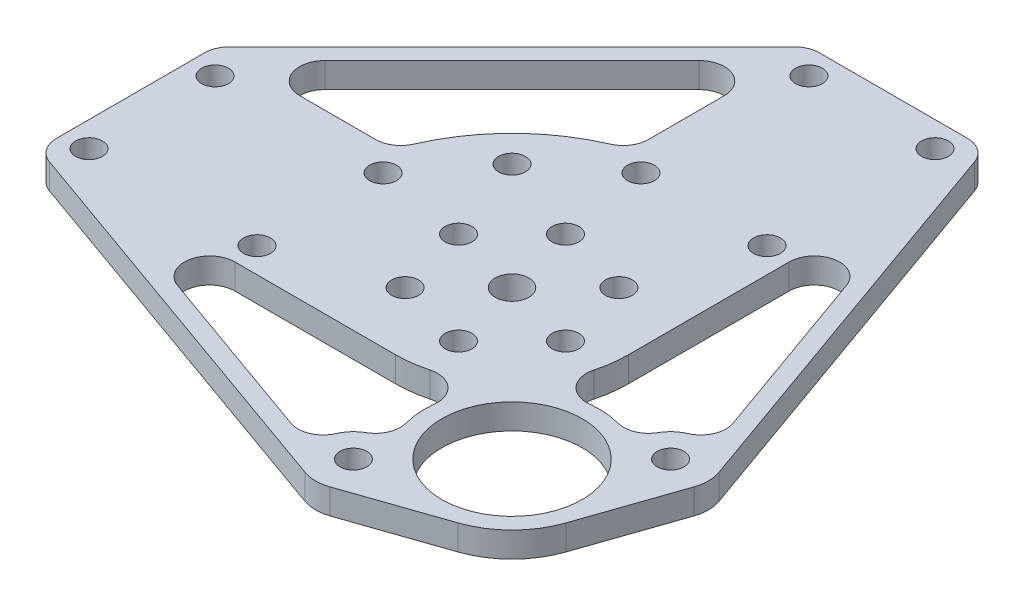
SolidWorks part; units mm, degrees
material "6061-T6 (SS)"
ref_plane "Front Plane" through (0, 0, 0) normal (0, 0, 1) x (1, 0, 0)
ref_plane "Top Plane" through (0, 0, 0) normal (0, 1, 0) x (1, 0, 0)
ref_plane "Right Plane" through (0, 0, 0) normal (1, 0, 0) x (0, 0, -1)
sketch "Sketch1" plane through (0, 0, 0) normal (0, 1, 0) x (1, 0, 0)
  line L0 (-14.5, -32) -> (14.5, -32) construction
  line L1 (10.85, 19.5) -> (-4.15, 19.5)
  line L2 (10.85, 19.5) -> (10.85, 39.5)
  line L3 (10.85, 39.5) -> (-4.15, 39.5)
  line L4 (-4.15, 19.5) -> (-4.15, 39.5)
  line L5 (10.85, 19.5) -> (-4.15, 39.5) construction
  line L6 (10.85, 39.5) -> (-4.15, 19.5) construction
  line L7 (-19.5, -10.85) -> (-39.5, -10.85)
  line L8 (-19.5, -10.85) -> (-19.5, 4.15)
  line L9 (-19.5, 4.15) -> (-39.5, 4.15)
  line L10 (-39.5, -10.85) -> (-39.5, 4.15)
  line L11 (-19.5, -10.85) -> (-39.5, 4.15) construction
  line L12 (-19.5, 4.15) -> (-39.5, -10.85) construction
  line L13 (20.7, 16) -> (-14, 16)
  line L14 (20.7, 16) -> (20.7, 43)
  line L15 (20.7, 43) -> (-14, 43)
  line L16 (-14, 16) -> (-14, 43)
  line L17 (20.7, 16) -> (-14, 43) construction
  line L18 (20.7, 43) -> (-14, 16) construction
  line L19 (-16, -20.7) -> (-43, -20.7)
  line L20 (-16, -20.7) -> (-16, 14)
  line L21 (-16, 14) -> (-43, 14)
  line L22 (-43, -20.7) -> (-43, 14)
  line L23 (-16, -20.7) -> (-43, 14) construction
  line L24 (-16, 14) -> (-43, -20.7) construction
  line L25 (10, -37) -> (-10, -37)
  line L26 (10, -37) -> (10, -27)
  line L27 (10, -27) -> (-10, -27)
  line L28 (-10, -37) -> (-10, -27)
  line L29 (10, -37) -> (-10, -27) construction
  line L30 (10, -27) -> (-10, -37) construction
  line L31 (37, -10) -> (27, -10)
  line L32 (37, -10) -> (37, 10)
  line L33 (37, 10) -> (27, 10)
  line L34 (27, -10) -> (27, 10)
  line L35 (37, -10) -> (27, 10) construction
  line L36 (37, 10) -> (27, -10) construction
  line L37 (32, 14.5) -> (32, -14.5) construction
  circle A0 centre (0, 0) radius 2
  circle A1 centre (0, 0) radius 9
  circle A2 centre (0, 0) radius 12.7
  point P3 (3.35, 29.5)
  point P8 (-29.5, -3.35)
  point P15 (0, -32)
  point P16 (-29.5, -3.35)
  point P17 (3.35, 29.5)
  point P30 (32, 0)
  point P38 (0, -32)
  point P41 (32, 0)
  dimension "D1" = 4
  dimension "D4" = 18
  dimension "D11" = 25.4
  dimension "D2" = 20
  dimension "D3" = 15
  dimension "D5" = 34.7
  dimension "D6" = 27
  dimension "D7" = 2
  dimension "D8" = 2
  dimension "D9" = 16
  dimension "D10" = 16
  dimension "D12" = 32
  dimension "D13" = 10
  dimension "D14" = 20
  dimension "D15" = 32
  dimension "D16" = 4.5
sketch "Sketch2" plane through (0, 0, 0) normal (0, 1, 0) x (1, 0, 0)
  line L3 (-16.5, -13.85) -> (-42.5, -13.85)
  line L4 (-42.5, -13.85) -> (-42.5, 7.15)
  line L5 (-42.5, 7.15) -> (-24.825, 24.825)
  line L6 (-19.5, -10.85) -> (-39.5, -10.85) construction
  line L9 (-39.5, -10.85) -> (-39.5, 4.15) construction
  line L10 (-19.5, -10.85) -> (-19.5, 4.15) construction
  line L12 (-19.5, 4.15) -> (-39.5, 4.15) construction
  line L16 (-16.5, -13.85) -> (-16.5, -29.1277)
  line L22 (16.9749, -34.4749) -> (25.7249, -25.7249)
  line L29 (25.7249, -25.7249) -> (-24.825, 24.825)
  line L39 (12, -27) -> (12, -39)
  line L40 (12, -39) -> (-12, -39)
  line L41 (-12, -39) -> (-12, -27)
  line L42 (12, -34.4495) -> (12, -39)
  line L43 (12, -39) -> (-12, -39)
  line L44 (-12, -39) -> (-12, -34.4495)
  arc A0 (-16.5, -29.1277) -> (-12, -34.4495) centre (-14.5, -32) ccw
  arc A2 (12, -34.4495) -> (16.9749, -34.4749) centre (14.5, -32) ccw
  dimension "D1" = 7
  dimension "D2" = 3
  dimension "D3" = 45
  dimension "D4" = 2
  dimension "D5" = 3
  dimension "D6" = 3
  dimension "D8" = 3
extrude "Boss-Extrude1" add sketch "Sketch2" along normal blind 3
mirror "Mirror5" about plane through (25.7249, 3, 25.7249) normal (-0.7071, 0, 0.7071) of bodies 101
hole_wizard "M3 Clearance Hole1" positions "Sketch3" profile "Sketch4" hole size "M3" standard "ANSI Metric" end condition up to next
sketch "Sketch3" plane through (0, 3, 0) normal (0, 1, 0) x (1, 0, 0)
  point P0 (-39.5, 4.15)
  point P3 (-19.5, 4.15)
  point P6 (-19.5, -10.85)
  point P9 (-39.5, -10.85)
  point P12 (-4.15, 19.5)
  point P15 (-4.15, 39.5)
  point P18 (10.85, 39.5)
  point P21 (10.85, 19.5)
sketch "Sketch4" plane through (-39.5, 3, -4.15) normal (1, 0, 0) x (0, 0, 1)
  line L0 (0, 0) -> (0, 3)
  line L1 (0, 3) -> (1.6, 3)
  line L2 (1.6, 3) -> (1.6, 0)
  line L5 (1.6, 0) -> (0, 0)
  line L11 (0, -6.35) -> (0, 107.95) construction
  dimension "Thru Hole Dia." = 3.2
  dimension "Thru Hole Depth" = 3
hole_wizard "M3 Clearance Hole2" positions "Sketch5" profile "Sketch6" hole size "M3" standard "ANSI Metric" end condition up to next
sketch "Sketch5" plane through (0, 3, 0) normal (0, 1, 0) x (1, 0, 0)
  line L4 (-8.6933, 2.3294) -> (-2.3294, 8.6933) construction
  line L5 (0, 0) -> (-5.5114, 5.5114) construction
  line L7 (-1000, 0) -> (49000, 0) construction
  circle A0 centre (0, 0) radius 9 construction
  point P23 (-2.3294, 8.6933)
  point P46 (6.364, 6.364)
  point P47 (8.6933, -2.3294)
  point P48 (2.3294, -8.6933)
  point P49 (-6.364, -6.364)
  point P50 (-8.6933, 2.3294)
  dimension "D1" = 45
  dimension "D2" = 6
sketch "Sketch6" plane through (-2.3294, 3, -8.6933) normal (1, 0, 0) x (0, 0, 1)
  line L0 (0, 0) -> (0, 3)
  line L1 (0, 3) -> (1.6, 3)
  line L2 (1.6, 3) -> (1.6, 0)
  line L5 (1.6, 0) -> (0, 0)
  line L11 (0, -6.35) -> (0, 107.95) construction
  dimension "Thru Hole Dia." = 3.2
  dimension "Thru Hole Depth" = 3
hole_wizard "Ø4.0 (4) Diameter Hole1" positions "Sketch7" profile "Sketch8" hole size "Ø4.0" standard "ANSI Metric" end condition up to next
sketch "Sketch7" plane through (0, 3, 0) normal (0, 1, 0) x (1, 0, 0)
  point P0 (0, 0)
sketch "Sketch8" plane through (0, 3, 0) normal (1, 0, 0) x (0, 0, 1)
  line L0 (0, 0) -> (0, 3)
  line L1 (0, 3) -> (2, 3)
  line L2 (2, 3) -> (2, 0)
  line L5 (2, 0) -> (0, 0)
  line L11 (0, -6.35) -> (0, 107.95) construction
  dimension "Thru Hole Dia." = 4
  dimension "Thru Hole Depth" = 3
sketch "Sketch13" plane through (0, 3, 0) normal (0, 1, 0) x (1, 0, 0)
  line L0 (-39.6716, 7.15) -> (-21.3337, 7.15)
  line L1 (0, 0) -> (-24.825, 24.825) construction
  line L2 (-7.15, 42.5) -> (-42.5, 7.15) construction
  line L4 (-23.4108, 23.4108) -> (-15.9099, 15.9099)
  line L5 (-5.7358, 41.0858) -> (-41.0858, 5.7358)
  line L6 (-23.4108, 23.4108) -> (-39.6716, 7.15)
  circle A2 centre (0, 0) radius 22.5 construction
  circle A3 centre (-19.5, 4.15) radius 1.6 construction
  arc A4 (-21.3337, 7.15) -> (-15.9099, 15.9099) centre (0, 0) cw
  dimension "D1" = 45
  dimension "D2" = 3
  dimension "D3" = 2
extrude "Cut-Extrude3" cut sketch "Sketch13" against normal up to surface (3 mm away) contours L0 A4 L4 L6 region at (-26.206, 3, -13.3731) up to face at (0, 0, 2)
mirror "Mirror6" about plane through (0, -28.7929, 0) normal (-0.7071, 0, 0.7071) of "Cut-Extrude3"
fillet "Fillet5" radius 3 4 edges at (-7.15, 1.5, -39.6716) (-7.15, 1.5, -21.3337) (-21.3337, 1.5, -7.15) (-39.6716, 1.5, -7.15)
hole_wizard "M3 Clearance Hole3" positions "Sketch14" profile "Sketch15" hole size "M3" standard "ANSI Metric" end condition up to next
sketch "Sketch14" plane through (0, 3, 0) normal (0, 1, 0) x (1, 0, 0)
  line L0 (-12.7279, 12.7279) -> (0, 0) construction
  line L2 (-12.2713, 34.5503) -> (-34.5503, 12.2713) construction
  circle A2 centre (-12.7279, 12.7279) radius 3
  point P0 (-12.7279, 12.7279)
  dimension "D1" = 6
  dimension "D2" = 18
sketch "Sketch15" plane through (-12.7279, 3, -12.7279) normal (1, 0, 0) x (0, 0, 1)
  line L0 (0, 0) -> (0, 3)
  line L1 (0, 3) -> (1.6, 3)
  line L2 (1.6, 3) -> (1.6, 0)
  line L5 (1.6, 0) -> (0, 0)
  line L11 (0, -6.35) -> (0, 107.95) construction
  dimension "Thru Hole Dia." = 3.2
  dimension "Thru Hole Depth" = 3
sketch "Sketch16" plane through (0, 3, 0) normal (0, 1, 0) x (1, 0, 0)
  line L0 (-16.5, -13.85) -> (-10.4933, -8.808)
  line L1 (13.85, 16.5) -> (8.808, 10.4933)
  line L16 (16.9749, -34.4749) -> (34.4749, -16.9749)
  line L17 (34.4495, -12) -> (39, -12)
  line L18 (39, -12) -> (39, 12)
  line L19 (39, 12) -> (34.4495, 12)
  line L20 (29.1277, 16.5) -> (13.85, 16.5)
  line L21 (13.85, 16.5) -> (13.85, 42.5)
  line L22 (13.85, 42.5) -> (-7.15, 42.5)
  line L23 (-7.15, 42.5) -> (-42.5, 7.15)
  line L24 (-42.5, 7.15) -> (-42.5, -13.85)
  line L25 (-42.5, -13.85) -> (-16.5, -13.85)
  line L26 (-16.5, -13.85) -> (-16.5, -29.1277)
  line L27 (-12, -34.4495) -> (-12, -39)
  line L28 (-12, -39) -> (12, -39)
  line L29 (12, -39) -> (12, -34.4495)
  line L30 (16.9749, -34.4749) -> (34.4749, -16.9749)
  line L31 (34.4495, -12) -> (39, -12)
  line L32 (39, -12) -> (39, 12)
  line L33 (39, 12) -> (34.4495, 12)
  line L34 (29.1277, 16.5) -> (13.85, 16.5)
  line L40 (-16.5, -13.85) -> (-16.5, -29.1277)
  line L41 (-12, -34.4495) -> (-12, -39)
  line L42 (-12, -39) -> (12, -39)
  line L43 (12, -39) -> (12, -34.4495)
  arc A0 (-10.4933, -8.808) -> (8.808, 10.4933) centre (0, 0) ccw
  arc A5 (34.4749, -16.9749) -> (34.4495, -12) centre (32, -14.5) ccw
  arc A6 (34.4495, 12) -> (29.1277, 16.5) centre (32, 14.5) ccw
  arc A7 (-16.5, -29.1277) -> (-12, -34.4495) centre (-14.5, -32) ccw
  arc A8 (12, -34.4495) -> (16.9749, -34.4749) centre (14.5, -32) ccw
  arc A9 (34.4749, -16.9749) -> (34.4495, -12) centre (32, -14.5) ccw
  arc A10 (34.4495, 12) -> (29.1277, 16.5) centre (32, 14.5) ccw
  arc A11 (-16.5, -29.1277) -> (-12, -34.4495) centre (-14.5, -32) ccw
  arc A12 (12, -34.4495) -> (16.9749, -34.4749) centre (14.5, -32) ccw
  dimension "D1" = 27.4
  dimension "D2" = 0
extrude "Cut-Extrude4" cut sketch "Sketch16" against normal up to surface (3 mm away) up to face at (-12.7279, 0, -11.1279)
sketch "Sketch17" plane through (0, 3, 0) normal (0, 1, 0) x (1, 0, 0)
  line L0 (0, 0) -> (17.6777, -17.6777) construction
  line L1 (-12.2713, 34.5503) -> (-34.5503, 12.2713) construction
  line L2 (-16.5, -13.85) -> (13.4837, -27.1399)
  line L3 (13.85, 16.5) -> (8.808, 10.4933) construction
  line L4 (-10.4933, -8.808) -> (-16.5, -13.85) construction
  line L5 (13.85, 16.5) -> (8.808, 10.4933)
  line L6 (-10.4933, -8.808) -> (-16.5, -13.85)
  line L7 (13.85, 16.5) -> (27.1399, -13.4837)
  arc A0 (13.4837, -27.1399) -> (27.1399, -13.4837) centre (17.6777, -17.6777) ccw
  circle A1 centre (17.6777, -17.6777) radius 8.35
  arc A2 (-10.4933, -8.808) -> (8.808, 10.4933) centre (0, 0) ccw construction
  arc A3 (-10.4933, -8.808) -> (8.808, 10.4933) centre (0, 0) ccw
  dimension "D1" = 2
  dimension "D2" = 20.7
  dimension "D3" = 25
extrude "Boss-Extrude2" add sketch "Sketch17" against normal up to surface (3 mm away) up to face at (-12.7279, 0, -11.1279)
sketch "Sketch18" plane through (0, 3, 0) normal (0, 1, 0) x (1, 0, 0)
  line L0 (8.2378, -27.1175) -> (27.1175, -8.2378) construction
  line L1 (-7.15, 42.5) -> (-42.5, 7.15) construction
  line L2 (31.3574, -6.73) -> (13.85, 42.5)
  line L3 (27.4632, -21.0491) -> (31.3721, -9.7037)
  line L4 (27.1399, -13.4837) -> (13.85, 16.5) construction
  line L5 (13.85, 42.5) -> (13.85, 16.5) construction
  line L6 (27.1399, -13.4837) -> (13.85, 16.5)
  line L7 (13.85, 42.5) -> (13.85, 16.5)
  line L8 (17.6777, -17.6777) -> (0, 0) construction
  line L9 (-42.5, -13.85) -> (-16.5, -13.85)
  line L10 (13.4837, -27.1399) -> (-16.5, -13.85)
  line L11 (21.0491, -27.4632) -> (9.7037, -31.3721)
  line L12 (6.73, -31.3574) -> (-42.5, -13.85)
  arc A0 (31.3721, -9.7037) -> (31.3574, -6.73) centre (27.1175, -8.2378) ccw
  arc A2 (13.4837, -27.1399) -> (27.1399, -13.4837) centre (17.6777, -17.6777) ccw construction
  arc A3 (27.4632, -21.0491) -> (27.1399, -13.4837) centre (17.6777, -17.6777) ccw
  arc A4 (21.0491, -27.4632) -> (13.4837, -27.1399) centre (17.6777, -17.6777) cw
  arc A5 (9.7037, -31.3721) -> (6.73, -31.3574) centre (8.2378, -27.1175) cw
  point P5 (17.6777, -17.6777)
  dimension "D2" = 9
  dimension "D1" = 13.35
extrude "Boss-Extrude3" add sketch "Sketch18" against normal up to surface (3 mm away) up to face at (-12.7279, 0, -11.1279)
hole_wizard "M3 Clearance Hole4" positions "Sketch19" profile "Sketch20" hole size "M3" standard "ANSI Metric" end condition up to next
sketch "Sketch19" plane through (0, 3, 0) normal (0, 1, 0) x (1, 0, 0)
  point P0 (8.2378, -27.1175)
  point P3 (27.1175, -8.2378)
sketch "Sketch20" plane through (8.2378, 3, 27.1175) normal (1, 0, 0) x (0, 0, 1)
  line L0 (0, 0) -> (0, 3)
  line L1 (0, 3) -> (1.6, 3)
  line L2 (1.6, 3) -> (1.6, 0)
  line L5 (1.6, 0) -> (0, 0)
  line L11 (0, -6.35) -> (0, 107.95) construction
  dimension "Thru Hole Dia." = 3.2
  dimension "Thru Hole Depth" = 3
sketch "Sketch21" plane through (0, 3, 0) normal (0, 1, 0) x (1, 0, 0)
  line L0 (13.85, 42.5) -> (13.85, 0) construction
  line L1 (0, 0) -> (24.9962, -24.9962) construction
  line L2 (13.85, 36.5311) -> (28.4268, -4.4581)
  line L3 (31.3574, -6.73) -> (13.85, 42.5) construction
  line L4 (11.9113, -9.0828) -> (11.105, -8.2766)
  line L5 (13.85, 0) -> (13.85, 36.5311)
  line L6 (0, -13.85) -> (-36.5311, -13.85)
  line L7 (9.0828, -11.9113) -> (8.2766, -11.105)
  line L8 (-36.5311, -13.85) -> (4.4581, -28.4268)
  arc A0 (11.105, -8.2766) -> (13.85, 0) centre (0, 0) ccw
  arc A1 (21.0491, -27.4632) -> (27.4632, -21.0491) centre (17.6777, -17.6777) ccw construction
  arc A2 (28.4268, -4.4581) -> (23.6465, -6.2498) centre (27.1175, -8.2378) ccw
  arc A3 (20.2869, -7.662) -> (23.6465, -6.2498) centre (21.0432, -4.7589) ccw
  arc A4 (7.662, -20.2869) -> (9.0828, -11.9113) centre (17.6777, -17.6777) cw
  circle A5 centre (17.6777, -17.6777) radius 10.35
  arc A6 (20.2869, -7.662) -> (11.9113, -9.0828) centre (17.6777, -17.6777) ccw
  arc A7 (7.662, -20.2869) -> (6.2498, -23.6465) centre (4.7589, -21.0432) cw
  arc A8 (4.4581, -28.4268) -> (6.2498, -23.6465) centre (8.2378, -27.1175) cw
  arc A9 (8.2766, -11.105) -> (0, -13.85) centre (0, 0) cw
  dimension "D1" = 8
  dimension "D5" = 3
  dimension "D2" = 2
  dimension "D4" = 2
  dimension "D3" = 2
extrude "Cut-Extrude5" cut sketch "Sketch21" against normal up to surface (3 mm away) up to face at (8.2378, 0, 28.7175)
fillet "Fillet6" radius 3 6 edges at (13.85, 1.5, -36.5311) (28.4268, 1.5, 4.4581) (11.105, 1.5, 8.2766) (-36.5311, 1.5, 13.85) (8.2766, 1.5, 11.105) (4.4581, 1.5, 28.4268)
fillet "Fillet7" radius 3 6 edges at (11.9113, 1.5, 9.0828) (9.0828, 1.5, 11.9113) (-42.5, 1.5, -7.15) (-7.15, 1.5, -42.5) (13.85, 1.5, -42.5) (-42.5, 1.5, 13.85)
